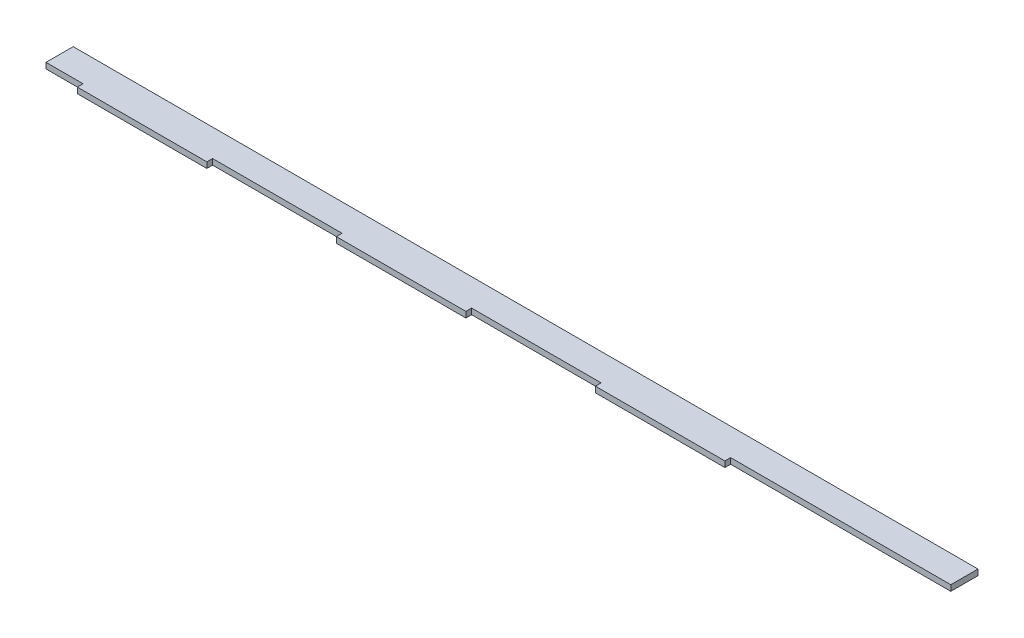
SolidWorks part; units mm, degrees
ref_plane "Front Plane" through (0, 0, 0) normal (0, 0, 1) x (1, 0, 0)
ref_plane "Top Plane" through (0, 0, 0) normal (0, 1, 0) x (1, 0, 0)
ref_plane "Right Plane" through (0, 0, 0) normal (1, 0, 0) x (0, 0, -1)
sketch "Sketch1" plane through (0, 0, 0) normal (0, 1, 0) x (1, 0, 0)
  line L17 (29.5571, 15) -> (29.5571, 0)
  line L18 (528.5571, 20) -> (528.5571, 0) construction
  line L19 (528.5571, 20) -> (528.5571, 0) construction
  line L33 (528.5571, 0) -> (528.5571, 15)
  line L34 (528.5571, 15) -> (29.5571, 15)
  line L44 (407.1286, -3.175) -> (407.1286, 0) construction
  line L45 (335.7, -3.175) -> (335.7, 0) construction
  line L46 (264.2714, -3.175) -> (264.2714, 0) construction
  line L47 (192.8429, -3.175) -> (192.8429, 0) construction
  line L48 (121.4143, -3.175) -> (121.4143, 0) construction
  line L49 (49.9857, -3.175) -> (49.9857, 0) construction
  line L50 (407.1286, -3.175) -> (407.1286, 0)
  line L51 (335.7, -3.175) -> (335.7, 0)
  line L52 (264.2714, -3.175) -> (264.2714, 0)
  line L53 (192.8429, -3.175) -> (192.8429, 0)
  line L54 (121.4143, -3.175) -> (121.4143, 0)
  line L55 (49.9857, -3.175) -> (49.9857, 0)
  line L56 (29.5571, 0) -> (49.9857, 0)
  line L57 (49.9857, -3.175) -> (121.4143, -3.175)
  line L58 (121.4143, 0) -> (192.8429, 0)
  line L59 (192.8429, -3.175) -> (264.2714, -3.175)
  line L60 (264.2714, 0) -> (335.7, 0)
  line L61 (335.7, -3.175) -> (407.1286, -3.175)
  line L62 (407.1286, 0) -> (528.5571, 0)
  dimension "D2" = 15
extrude "Boss-Extrude1" add sketch "Sketch1" along normal blind 3.175
